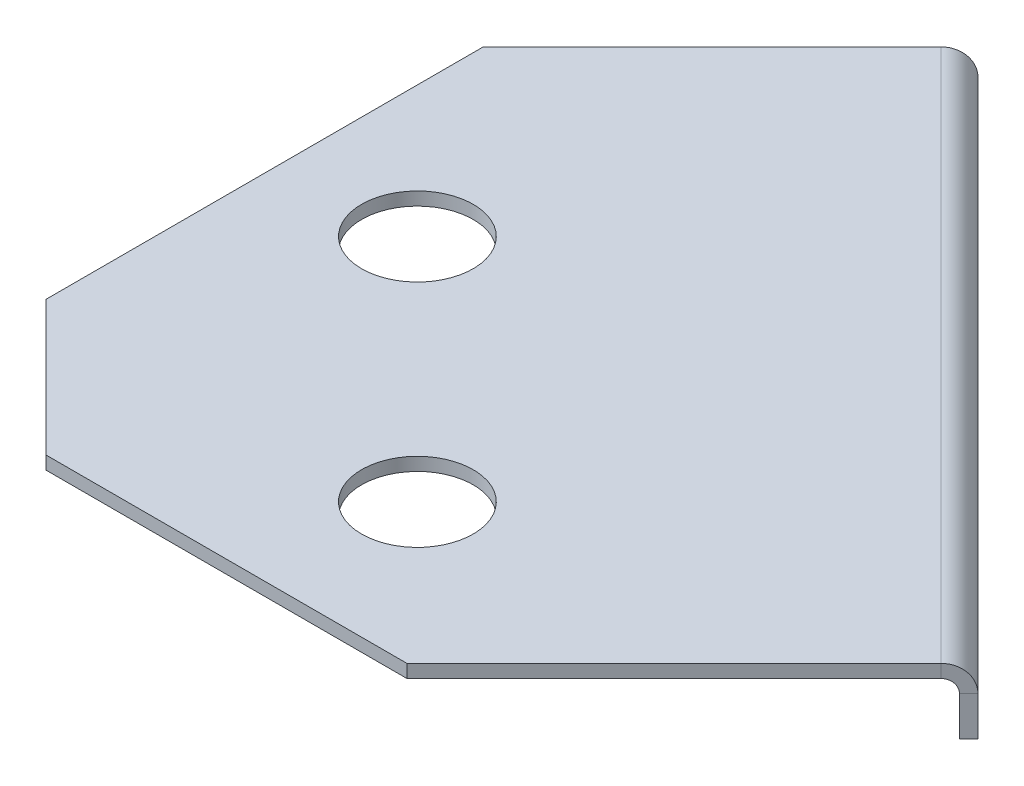
SolidWorks part; units mm, degrees
note: The reader was unsure of these and kept them because the rebuilt part matched: thickness of "Base-Flange1", "Edge-Flange1", "Sheet-Metal3", "Sheet-Metal4", "Sheet-Metal5"; flange length of "Edge-Flange1".
ref_plane "Front Plane" through (0, 0, 0) normal (0, 0, 1) x (1, 0, 0)
ref_plane "Top Plane" through (0, 0, 0) normal (0, 1, 0) x (1, 0, 0)
ref_plane "Right Plane" through (0, 0, 0) normal (1, 0, 0) x (0, 0, -1)
sketch "Sketch1" plane through (0, 0, 0) normal (0, 1, 0) x (1, 0, 0)
  line L0 (-5.2272, 5.6721) -> (-5.2272, 7.0213) construction
  line L1 (-5.2272, 7.0213) -> (-8.5, 7.0213) construction
  line L2 (-8.5, 7.0213) -> (-8.5, -7.0213) construction
  line L3 (-8.5, -7.0213) -> (8.5, -7.0213) construction
  line L4 (8.5, -7.0213) -> (8.5, -3.1668) construction
  line L5 (8.5, -3.1668) -> (3.6116, -3.1668) construction
  line L6 (1.4903, -5.2881) -> (-7.3485, 3.5508) construction
  line L7 (-5.2272, 5.6721) -> (3.6116, -3.1668) construction
  line L8 (-4.8737, 5.3185) -> (-8.5, 1.6922)
  line L9 (-8.5, 1.6922) -> (-8.5, -4.9679)
  line L10 (-8.5, -4.9679) -> (-6.4467, -7.0213)
  line L11 (-6.4467, -7.0213) -> (-0.95, -7.0213)
  line L12 (-0.95, -7.0213) -> (3.2581, -2.8132)
  line L13 (3.2581, -2.8132) -> (-4.8737, 5.3185)
  arc A0 (-5.2272, 5.6721) -> (-7.3485, 3.5508) centre (-6.2879, 4.6114) ccw construction
  arc A1 (1.4903, -5.2881) -> (3.6116, -3.1668) centre (2.551, -4.2274) ccw construction
  dimension "D7" = 1.5
  dimension "D1" = 14.0425
  dimension "D2" = 3.2728
  dimension "D3" = 1.3492
  dimension "D4" = 1.5
  dimension "D5" = 3.8545
  dimension "D6" = 17
  dimension "D8" = 0.5
  dimension "D9" = 0.5
  dimension "D10" = 45
base flange "Base-Flange1" sketch "Sketch1" thickness 0.2 reverse thickness direction no parameters "D1"=1.5
edge flange "Edge-Flange1" sketch "Sketch9" flange angle 90 flange length 1 flange position material outside bend radius 0.2 thickness 0.2 relief rectangular parameters "D6"=10
sketch "Sketch9" plane through (0.2224, -0.2, -0.2224) normal (0.7071, 0, -0.7071) x (0.7071, 0, 0.7071)
  line L0 (4.293, 0) -> (-7.207, 0) construction
  line L1 (4.293, 0) -> (-7.207, 0)
  line L2 (-7.207, 0) -> (-7.207, 0.8)
  line L3 (-7.207, 0.8) -> (4.293, 0.8)
  line L4 (4.293, 0.8) -> (4.293, 0)
bend "EdgeBend1" bend radius 0.2 bend angle 90 parameters "D5"=1
hole_wizard "Ø1.7 (1.7) Diameter Hole1" positions "Sketch10" profile "Sketch11" hole size "Ø1.7" standard "ANSI Metric" end condition up to next
sketch "Sketch10" plane through (0, 0, 0) normal (0, 1, 0) x (1, 0, 0)
  line L0 (-8.5, -4.9679) -> (-6.4467, -7.0213) construction
  line L1 (-8.5, 1.6922) -> (-8.5, -4.9679) construction
  point P0 (-6.5, -1.3111)
  point P2 (-3, -4.8111)
  dimension "D1" = 4
  dimension "D2" = 4
  dimension "D3" = 2
  dimension "D4" = 5.5
sketch "Sketch11" plane through (-6.5, 0, 1.3111) normal (1, 0, 0) x (0, 0, 1)
  line L0 (0, 0) -> (0, 0.2)
  line L1 (0, 0.2) -> (0.85, 0.2)
  line L2 (0.85, 0.2) -> (0.85, 0)
  line L5 (0.85, 0) -> (0, 0)
  line L11 (0, -6.35) -> (0, 107.95) construction
  dimension "Thru Hole Dia." = 1.7
  dimension "Thru Hole Depth" = 0.2
sketch "Bend-Lines1" [suppressed] plane through (0, 0, 0) normal (0, 1, 0) x (1, 0, 0)
sketch "Bounding-Box1" [suppressed] plane through (0, 0, 0) normal (0, 1, 0) x (1, 0, 0)
sheet metal parameters "Sheet-Metal3" thickness 0.2 parameters "D1"=1.5, "D7"=0.5
flat pattern "Flat-Pattern3" [suppressed]
sketch "Bend-Lines2" plane through (0, 0, 0) normal (0, 1, 0) x (1, 0, 0)
sketch3d "Bounding-Box2" [suppressed]
  line L0 (11.83, -1.6379, 0) -> (3.6983, -9.7696, 0) construction
  line L1 (4.8737, 5.3185, 0) -> (-3.2581, -2.8132, 0) construction
  line L2 (11.83, -1.6379, 0) -> (4.8737, 5.3185, 0) construction
  line L3 (3.6983, -9.7696, 0) -> (-3.2581, -2.8132, 0) construction
sheet metal parameters "Sheet-Metal4" thickness 0.2 parameters "D1"=1.5, "D7"=0.5
flat pattern "Flat-Pattern3"
sketch "Bend-Lines2" plane through (0, 0, 0) normal (0, 1, 0) x (1, 0, 0)
  line L0 (3.2833, -2.788) -> (-4.8485, 5.3437) construction
  line L1 (3.2833, -2.788) -> (-4.8485, 5.3437) construction
sketch3d "Bounding-Box2" [suppressed]
  line L0 (-11.83, -1.6379, 0) -> (-3.6983, -9.7696, 0) construction
  line L1 (-4.2576, 5.9346, 0) -> (3.8741, -2.1971, 0) construction
  line L2 (-11.83, -1.6379, 0) -> (-4.2576, 5.9346, 0) construction
  line L3 (-3.6983, -9.7696, 0) -> (3.8741, -2.1971, 0) construction
bend of the flat pattern "Flatten-<EdgeBend1>1"
sheet metal parameters "Sheet-Metal5" thickness 0.2 parameters "D1"=1.5, "D7"=0.5
flat pattern "Flat-Pattern3"
sketch "Bend-Lines2" plane through (0, 0, 0) normal (0, 1, 0) x (1, 0, 0)
  line L0 (3.2833, -2.788) -> (-4.8485, 5.3437) construction
  line L1 (3.2833, -2.788) -> (-4.8485, 5.3437) construction
sketch3d "Bounding-Box2" [suppressed]
  line L0 (-11.83, -1.6379, 0) -> (-3.6983, -9.7696, 0) construction
  line L1 (-4.2576, 5.9346, 0) -> (3.8741, -2.1971, 0) construction
  line L2 (-11.83, -1.6379, 0) -> (-4.2576, 5.9346, 0) construction
  line L3 (-3.6983, -9.7696, 0) -> (3.8741, -2.1971, 0) construction
bend of the flat pattern "Flatten-<EdgeBend1>1"
